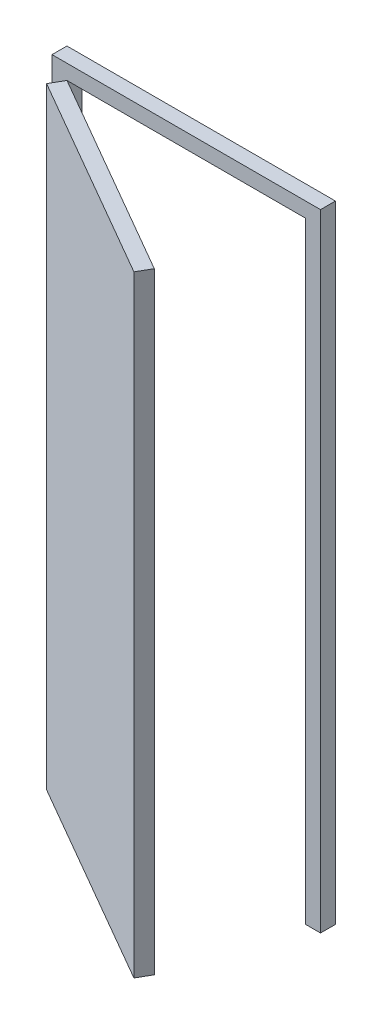
SolidWorks part; units mm, degrees
ref_plane "Front" through (0, 0, 0) normal (0, 0, 1) x (1, 0, 0)
ref_plane "Top" through (0, 0, 0) normal (0, 1, 0) x (1, 0, 0)
ref_plane "Right" through (0, 0, 0) normal (1, 0, 0) x (0, 0, -1)
sketch "Sketch1" plane through (0, 0, 0) normal (0, 0, 1) x (1, 0, 0)
  line L0 (812.8, 2032) -> (812.8, -2133.6)
  line L1 (-914.4, 2133.6) -> (914.4, 2133.6)
  line L2 (-914.4, 2133.6) -> (-914.4, -2133.6)
  line L3 (-914.4, -2133.6) -> (914.4, -2133.6) construction
  line L4 (914.4, 2133.6) -> (914.4, -2133.6)
  line L5 (-914.4, 2133.6) -> (914.4, -2133.6) construction
  line L6 (-914.4, -2133.6) -> (914.4, 2133.6) construction
  line L7 (-812.8, 2032) -> (812.8, 2032)
  line L8 (-812.8, 2032) -> (-812.8, -2133.6)
  line L9 (-914.4, -2133.6) -> (-812.8, -2133.6)
  line L10 (812.8, -2133.6) -> (914.4, -2133.6)
  point P0 (0, 0)
  dimension "D1" = 4267.2
  dimension "D3" = 1828.8
  dimension "D2" = 101.6
extrude "Boss-Extrude1" add sketch "Sketch1" along normal blind 101.6
sketch "Sketch2" plane through (0, -2133.6, 0) normal (0, -1, 0) x (1, 0, 0)
  line L0 (-812.8, 101.6) -> (595.0109, 914.4)
  line L1 (595.0109, 914.4) -> (544.2109, 1002.3882)
  line L2 (544.2109, 1002.3882) -> (-863.6, 189.5882)
  line L3 (-863.6, 189.5882) -> (-812.8, 101.6)
  line L4 (-812.8, 0) -> (812.8, 0) construction
  dimension "D1" = 101.6
  dimension "D2" = 30
extrude "Boss-Extrude2" add sketch "Sketch2" against normal up to surface (4165.6 mm away) separate body up to face at (0, 2032, 50.8)
